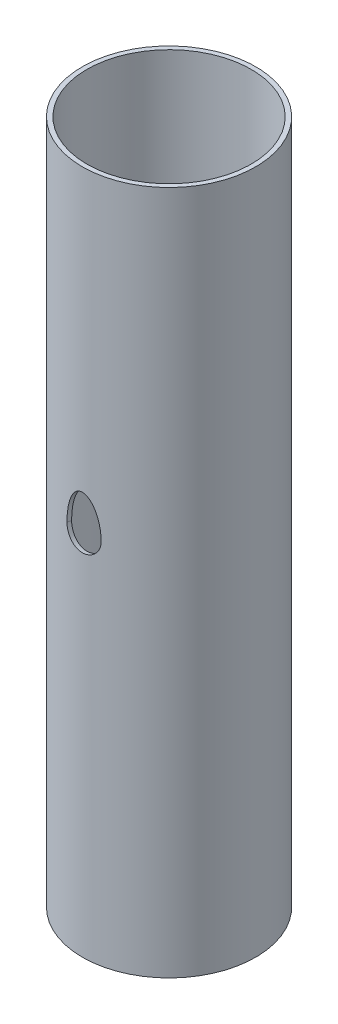
SolidWorks part; units mm, degrees
ref_plane "Front Plane" through (0, 0, 0) normal (0, 0, 1) x (1, 0, 0)
ref_plane "Top Plane" through (0, 0, 0) normal (0, 1, 0) x (1, 0, 0)
ref_plane "Right Plane" through (0, 0, 0) normal (1, 0, 0) x (0, 0, -1)
sketch "Sketch2" plane through (0, 0, 0) normal (0, 1, 0) x (1, 0, 0)
  circle A0 centre (0, 0) radius 36
  circle A1 centre (0, 0) radius 38
  dimension "D1" = 2
  dimension "D2" = 76
extrude "Boss-Extrude1" add sketch "Sketch2" along normal blind 300
ref_axis "Axis1" through (41.8, 0, 0) along (-1, 0, 0)
ref_plane "Plane1" through (0, 0, 0) normal (0, 0.2045, 0.9789) x (-1, 0, 0)
sketch "Sketch3" plane through (0, 0, 0) normal (0, 0.2045, 0.9789) x (-1, 0, 0)
  line L0 (0, 41.8) -> (0, -41.8) construction
  line L2 (-41.8, 0) -> (41.8, 0) construction
  arc A0 (7.5, -150) -> (-7.5, -150) centre (0, -150) ccw
  arc A1 (-7.5, -150) -> (7.5, -150) centre (0, -150) ccw construction
  ellipse E0 centre (0, -150) end of major axis (0, -165) minor radius 7.5 (-7.5, -150) -> (7.5, -150) ccw
  point P1 (0, -135)
  point P7 (-7.5, -150)
  dimension "D1" = 15
  dimension "D2" = 150
  dimension "D3" = 15
extrude "Cut-Extrude1" cut sketch "Sketch3" along normal up to next
